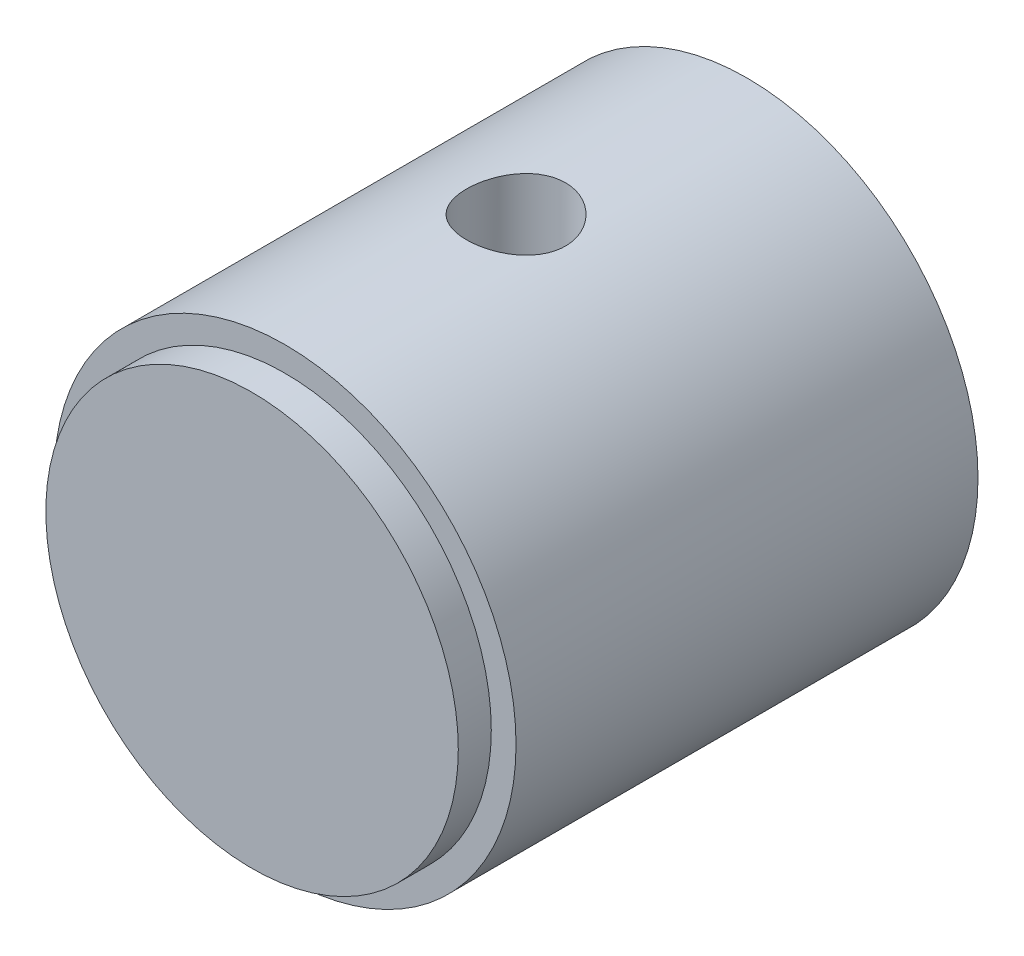
SolidWorks part; units mm, degrees
ref_plane "Front Plane" through (0, 0, 0) normal (0, 0, 1) x (1, 0, 0)
ref_plane "Top Plane" through (0, 0, 0) normal (0, 1, 0) x (1, 0, 0)
ref_plane "Right Plane" through (0, 0, 0) normal (1, 0, 0) x (0, 0, -1)
sketch "Sketch1" plane through (0, 0, 0) normal (0, 0, 1) x (1, 0, 0)
  line L0 (-17.8629, 0) -> (23.0543, 0) construction
  line L1 (0, -13.76) -> (0, 13.0902) construction
  circle A0 centre (0, 0) radius 7
  circle A1 centre (0, 0) radius 6.25
  dimension "D1" = 14
  dimension "D2" = 12.5
extrude "Boss-Extrude1" add sketch "Sketch1" along normal mid plane 14 contours A0
extrude "Boss-Extrude2" add sketch "Sketch1<3>" along normal blind 8 contours A1
sketch "Sketch1<3>" plane through (0, 0, 0) normal (0, 0, 1) x (1, 0, 0) same geometry as "Sketch1"
hole_wizard "Ø1.0mm Dowel Hole1" positions "Sketch5" profile "Sketch6" hole size "Ø1.0" standard "ISO"
sketch "Sketch5" plane through (0, 0, -7) normal (0, 0, -1) x (-1, 0, 0)
  point P0 (0, 0)
sketch "Sketch6" plane through (0, 0, -7) normal (1, 0, 0) x (0, 1, 0)
  line L0 (0, 0) -> (0, 13.8541)
  line L1 (0, 13.8541) -> (4.75, 11)
  line L2 (4.75, 11) -> (4.75, 0)
  line L5 (4.75, 0) -> (0, 0)
  line L10 (0, 13.8541) -> (-4.75, 11) construction
  line L11 (0, -6.35) -> (0, 107.95) construction
  dimension "Hole Dia." = 9.5
  dimension "Hole Depth" = 11
  dimension "Drill Angle" = 118
hole_wizard "CSK for M1.6 Countersunk Flat Head Screw1" positions "Sketch7" profile "Sketch8" countersink size "M1.6" standard "ISO"
sketch "Sketch7" plane through (0, 0, -7) normal (0, 0, -1) x (-1, 0, 0)
  point P0 (0, 0)
sketch "Sketch8" plane through (0, 0, -7) normal (1, 0, 0) x (0, 1, 0)
  line L0 (0, 0) -> (0, 13.8541)
  line L1 (0, 13.8541) -> (4.75, 11)
  line L2 (4.75, 11) -> (4.75, 3.9838)
  line L3 (4.75, 3.9838) -> (6.2, 0)
  line L5 (6.2, 0) -> (0, 0)
  line L6 (-4.75, 3.9838) -> (-6.2, 0) construction
  line L10 (0, 13.8541) -> (-4.75, 11) construction
  line L11 (0, -6.35) -> (0, 107.95) construction
  dimension "Hole Dia." = 9.5
  dimension "Hole Depth" = 11
  dimension "Near C'Sink Dia." = 12.4
  dimension "Near C'Sink Angle" = 40
  dimension "Drill Angle" = 118
sketch "Sketch10" plane through (0, 0, 0) normal (0, 1, 0) x (1, 0, 0)
  line L0 (0, -13.1296) -> (0, 11.2615) construction
  line L1 (6.2, 7) -> (-6.2, 7) construction
  circle A0 centre (0, 0) radius 1.5
  dimension "D1" = 3
  dimension "D2" = 7
extrude "Cut-Extrude1" cut sketch "Sketch10" against normal mid plane 18
